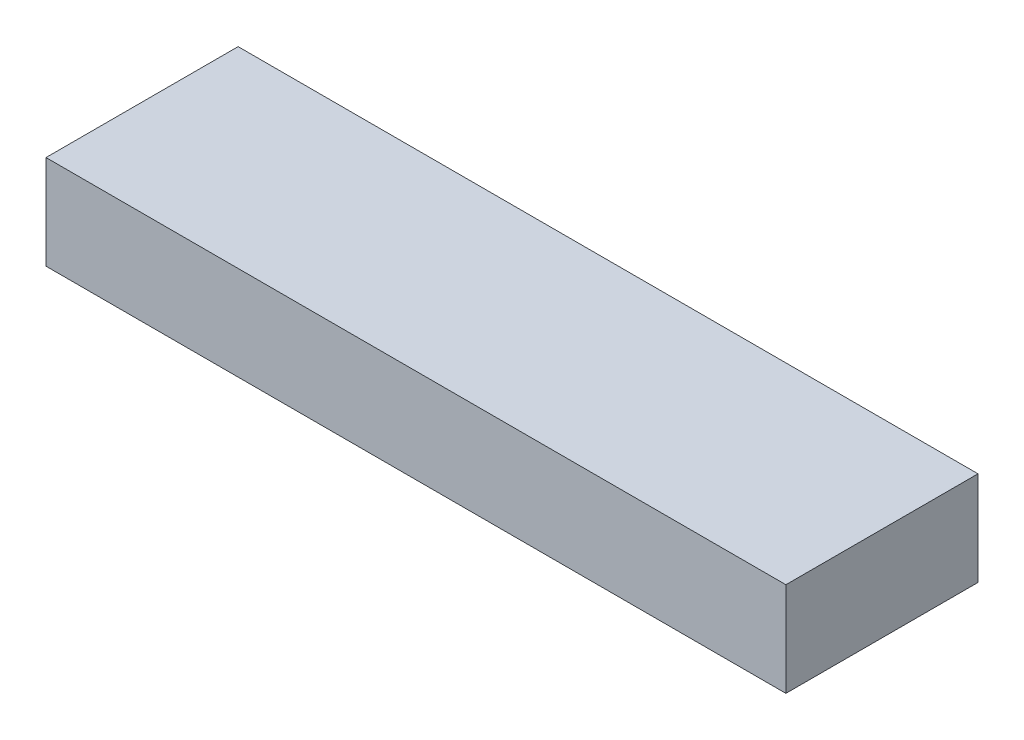
SolidWorks part; units mm, degrees
ref_plane "Front Plane" through (0, 0, 0) normal (0, 0, 1) x (1, 0, 0)
ref_plane "Top Plane" through (0, 0, 0) normal (0, 1, 0) x (1, 0, 0)
ref_plane "Right Plane" through (0, 0, 0) normal (1, 0, 0) x (0, 0, -1)
sketch "Sketch1" plane through (0, 0, 0) normal (0, 1, 0) x (1, 0, 0)
  line L1 (570, -148) -> (-570, -148)
  line L2 (570, -148) -> (570, 148)
  line L3 (570, 148) -> (-570, 148)
  line L4 (-570, -148) -> (-570, 148)
  line L5 (570, -148) -> (-570, 148) construction
  line L6 (570, 148) -> (-570, -148) construction
  point P0 (0, 0)
  dimension "D1" = 1140
  dimension "D2" = 296
extrude "Boss-Extrude1" add sketch "Sketch1" along normal blind 145
equation "\"thickness 1\" = 2"
equation "\"thickness 2\"= 3"
equation "\"connecting flange\"= 35"
equation "\"main length\"= 1200"
equation "\"main width\"= 1200"
equation "\"divider panel distance offset\"= 296"
equation "\"access hatch length\" = \"access hatch cutout length\" + \"access hatch offset\" * 2"
equation "\"access hatch width\" = \"access hatch cutout width\" + \"access hatch offset\" * 2"
equation "\"side panel length\"= 1200"
equation "\"side panel width\"= 950"
equation "\"drift eliminator size offset\"= 5"
equation "\"drift eliminator depth\" = \"divider panel distance offset\""
equation "\"D2@Sketch1\"=\"drift eliminator depth\""
equation "\"thickness radius 1\"= 3.7366"
equation "\"connecting flange holes\"= 8"
equation "\"connecting flange hole gap\"= 100"
equation "\"cut out flange\"= 15 "
equation "\"top panel slot length\"= 250"
equation "\"top panel slot width\"= 700"
equation "\"access hatch cutout length\"= 400"
equation "\"access hatch cutout width\"= 600"
equation "\"access hatch cutout offset X\"= 100"
equation "\"access hatch cutout offset Y\"= 100"
equation "\"slotted panel length\" = \"main length\" + 100"
equation "\"slotted panel width\" = \"main width\""
equation "\"slot count x\"= 4"
equation "\"slot count y\"= 9"
equation "\"slot offset\" = \"water tray depth\""
equation "\"slot length\"= 30"
equation "\"slot width\"= 200"
equation "\"slot offset x\" = \"slot length\" + \"slot offset\""
equation "\"slot offset y\" = \"slot width\" + \"slot offset\""
equation "\"guide rail flange\"= 40"
equation "\"guid rail flange mount side\"= 20"
equation "\"guid rail back length\" = \"main width\" - \"guide rail flange\" * 2"
equation "\"splash plate length\"= 400"
equation "\"splash plate width\" = \"main width\""
equation "\"splash plate air gap\"= 200"
equation "\"splash plate slot count\"= 11"
equation "\"splash plate slot length\"= 50"
equation "\"splash plate slot height\"= 50"
equation "\"splash plate slot offset\"= 65"
equation "\"water tray depth\"= 150"
equation "\"water tray width\"= 200"
equation "\"water tray panel length\"= 473"
equation "\"dimpled panel length\" = \"main length\" - 200 - \"water tray depth\"/2"
equation "\"dimpled panel top offset\" = \"water tray depth\"/2"
equation "\"dimpled panel width\" = \"main width\""
equation "\"dimple panel slot count\"= 119"
equation "\"dimple panel slot length\"= 10"
equation "\"dimple panel slot width\"= 5"
equation "\"dimple panel slot offset\"= 10"
equation "\"sump base flat section width\"= 300"
equation "\"sump upper depth\"= 300"
equation "\"sump depth\"= 550"
equation "\"leg length\" = \"sump depth\" + 150"
equation "\"leg width\"= 80"
equation "\"leg depth\"= 40"
equation "\"leg support plate size\" = \"leg width\" - \"thickness 2\" * 2"
equation "\"leg base plate thickness\"= 8"
